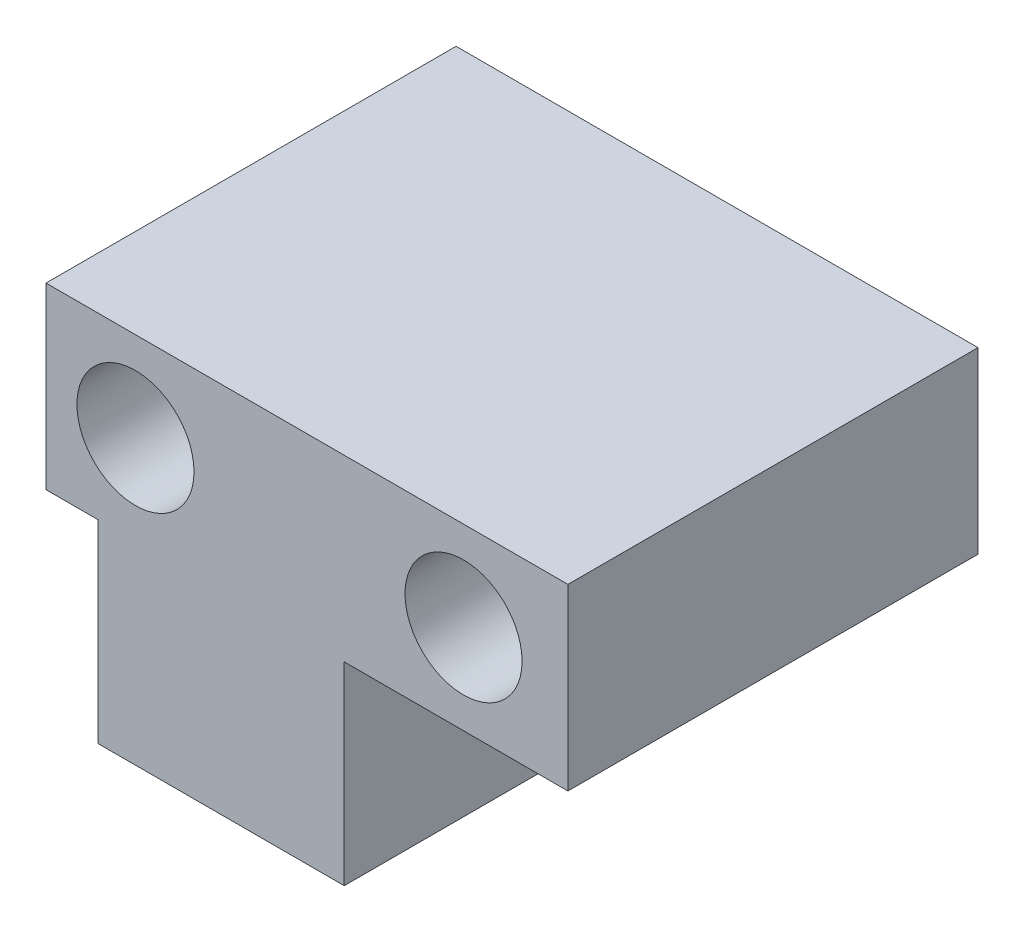
SolidWorks part; units mm, degrees
ref_plane "Plan de face" through (0, 0, 0) normal (0, 0, 1) x (1, 0, 0)
ref_plane "Plan de dessus" through (0, 0, 0) normal (0, 1, 0) x (1, 0, 0)
ref_plane "Plan de droite" through (0, 0, 0) normal (1, 0, 0) x (0, 0, -1)
sketch "Esquisse1" plane through (0, 0, 0) normal (0, 0, 1) x (1, 0, 0)
  line L1 (0, 0) -> (70, 0)
  line L2 (0, 0) -> (0, 24)
  line L3 (0, 24) -> (70, 24)
  line L4 (70, 0) -> (70, 24)
  dimension "D2" = 24
  dimension "D1" = 70
extrude "Boss.-Extru.1" add sketch "Esquisse1" along normal blind 55
sketch "Esquisse2" plane through (0, 0, 0) normal (0, 0, 1) x (1, 0, 0)
  line L0 (0, 24) -> (0, 0) construction
  line L2 (70, 24) -> (0, 24) construction
  circle A0 centre (56, 12) radius 7.85
  circle A1 centre (12, 12) radius 7.85
  dimension "D1" = 44
  dimension "D2" = 15.7
  dimension "D3" = 15.7
  dimension "D4" = 12
  dimension "D6" = 12
  dimension "D5" = 12
extrude "Enlèv. mat.-Extru.1" cut sketch "Esquisse2" along normal through all
sketch "Esquisse6" plane through (0, 0, 0) normal (0, -1, 0) x (1, 0, 0)
  line L0 (0, 0) -> (70, 0) construction
  line L1 (7, 0) -> (40, 0)
  line L2 (7, 0) -> (7, 5)
  line L3 (7, 5) -> (35, 5)
  line L4 (35, 5) -> (35, 50)
  line L5 (0, 55) -> (70, 55) construction
  line L6 (7, 55) -> (40, 55)
  line L7 (7, 55) -> (7, 50)
  line L8 (7, 50) -> (35, 50)
  line L9 (40, 0) -> (40, 55)
  line L10 (0, 55) -> (0, 0) construction
  dimension "D1" = 7
  dimension "D2" = 5
  dimension "D3" = 5
  dimension "D4" = 7
  dimension "D5" = 5
  dimension "D6" = 33
extrude "Boss.-Extru.3" add sketch "Esquisse6" along normal blind 21
sketch "Esquisse9" plane through (0, -21, 0) normal (0, -1, 0) x (1, 0, 0)
  line L1 (40, 55) -> (7, 55)
  line L2 (40, 55) -> (40, 0)
  line L3 (40, 0) -> (7, 0)
  line L4 (7, 55) -> (7, 0)
extrude "Boss.-Extru.4" add sketch "Esquisse9" along normal blind 5
sketch "Esquisse10" plane through (7, 0, 0) normal (-1, 0, 0) x (0, 0, 1)
  line L0 (5, 0) -> (0, 0) construction
  line L1 (55, 0) -> (50, 0) construction
  line L2 (50, -21) -> (50, 0) construction
  line L3 (0, -26) -> (0, 0) construction
  circle A0 centre (52.5, -16) radius 1.5
  circle A1 centre (52.5, -4) radius 1.5
  circle A2 centre (2.5, -16) radius 1.5
  circle A3 centre (2.5, -4) radius 1.5
  dimension "D1" = 3
  dimension "D2" = 3
  dimension "D3" = 3
  dimension "D4" = 3
  dimension "D5" = 16
  dimension "D6" = 4
  dimension "D7" = 4
  dimension "D8" = 16
  dimension "D9" = 2.5
  dimension "D10" = 2.5
  dimension "D11" = 2.5
  dimension "D12" = 2.5
extrude "Enlèv. mat.-Extru.4" cut sketch "Esquisse10" against normal blind 4
